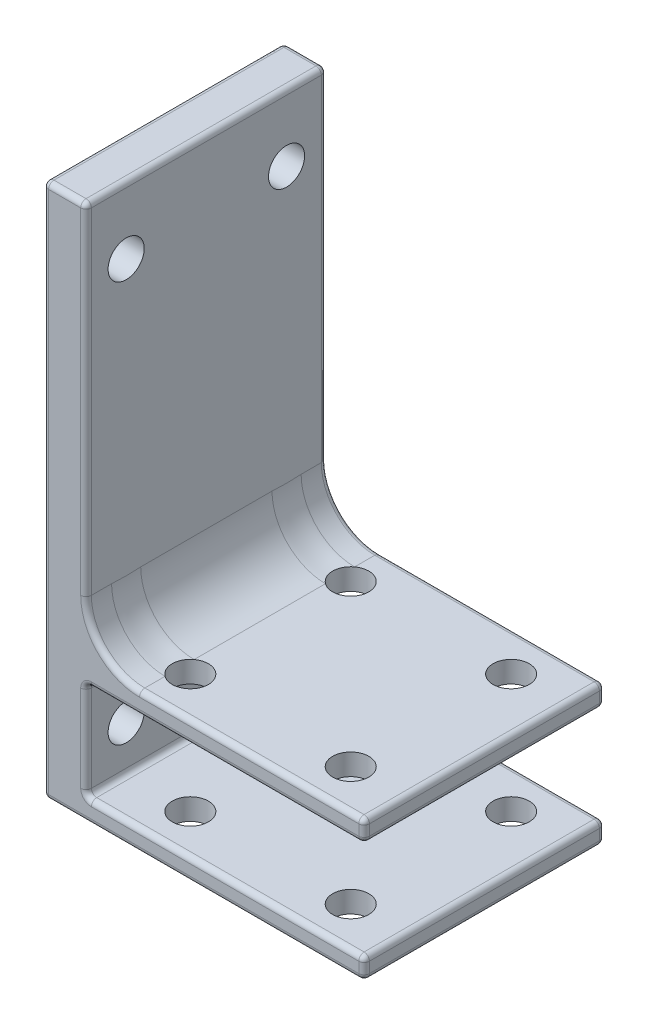
SolidWorks part; units mm, degrees
material "Nylon 6/10"
ref_plane "Front Plane" through (0, 0, 0) normal (0, 0, 1) x (1, 0, 0)
ref_plane "Top Plane" through (0, 0, 0) normal (0, 1, 0) x (1, 0, 0)
ref_plane "Right Plane" through (0, 0, 0) normal (1, 0, 0) x (0, 0, -1)
sketch "Sketch1" plane through (0, 0, 0) normal (0, 0, 1) x (1, 0, 0)
  line L0 (0, 0) -> (0, 100)
  line L1 (0, 100) -> (8, 100)
  line L2 (8, 100) -> (8, 4)
  line L3 (8, 4) -> (60, 4)
  line L4 (60, 4) -> (60, 0)
  line L5 (60, 0) -> (0, 0)
  dimension "D1" = 4
  dimension "D2" = 60
  dimension "D3" = 8
  dimension "D4" = 100
extrude "base" add sketch "Sketch1" along normal blind 45
sketch "Sketch2" plane through (8, 0, 0) normal (1, 0, 0) x (0, 0, -1)
  line L0 (-45, 4) -> (-45, 100) construction
  line L1 (-45, 26.25) -> (0, 26.25)
  line L2 (-45, 26.25) -> (-45, 22.25)
  line L3 (-45, 22.25) -> (0, 22.25)
  line L4 (0, 26.25) -> (0, 22.25)
  line L5 (0, 4) -> (0, 100) construction
  line L6 (-45, 4) -> (0, 4) construction
  dimension "D1" = 4
  dimension "D2" = 18.25
extrude "top skin" add sketch "Sketch2" along normal up to surface (52 mm away) up to face at (60, 2, 22.5)
hole_wizard "slider bolt hole pattern" positions "Sketch3" profile "Sketch4" hole size "1/4" standard "ANSI Inch" end condition through all
sketch "Sketch3" plane through (8, 0, 0) normal (1, 0, 0) x (0, 0, -1)
  line L1 (-37.5, 87.5) -> (-7.5, 87.5)
  line L2 (-37.5, 87.5) -> (-37.5, 12.5)
  line L3 (-37.5, 12.5) -> (-7.5, 12.5)
  line L4 (-7.5, 87.5) -> (-7.5, 12.5)
  line L5 (-22.5, 12.5) -> (-22.5, 0) construction
  line L6 (-45, 0) -> (0, 0) construction
  line L8 (-22.5, 87.5) -> (-22.5, 100) construction
  line L9 (-45, 100) -> (0, 100) construction
  point P0 (-37.5, 87.5)
  point P1 (-7.5, 12.5)
  point P60 (-37.5, 12.5)
  point P61 (-7.5, 87.5)
  dimension "D1" = 75
  dimension "D2" = 30
sketch "Sketch4" plane through (8, 87.5, 37.5) normal (0, 1, 0) x (0, 0, -1)
  line L0 (0, 0) -> (0, 8)
  line L1 (0, 8) -> (3.3782, 8)
  line L2 (3.3782, 8) -> (3.3782, 0)
  line L5 (3.3782, 0) -> (0, 0)
  line L11 (0, -6.35) -> (0, 107.95) construction
  dimension "Thru Hole Dia." = 6.7564
  dimension "Thru Hole Depth" = 8
hole_wizard "desktop bolt hole pattern" positions "Sketch5" profile "Sketch6" hole size "1/4" standard "ANSI Inch" end condition through all
sketch "Sketch5" plane through (0, 26.25, 0) normal (0, 1, 0) x (1, 0, 0)
  line L1 (20, -7.5) -> (50, -7.5)
  line L2 (20, -7.5) -> (20, -37.5)
  line L3 (20, -37.5) -> (50, -37.5)
  line L4 (50, -7.5) -> (50, -37.5)
  line L5 (50, -22.5) -> (60, -22.5)
  line L6 (60, -45) -> (60, 0) construction
  point P1 (20, -7.5)
  point P2 (50, -37.5)
  point P97 (20, -37.5)
  point P98 (50, -7.5)
  dimension "D2" = 30
  dimension "D1" = 10
  dimension "D3" = 30
sketch "Sketch6" plane through (20, 26.25, 7.5) normal (1, 0, 0) x (0, 0, 1)
  line L0 (0, 0) -> (0, 26.25)
  line L1 (0, 26.25) -> (3.3782, 26.25)
  line L2 (3.3782, 26.25) -> (3.3782, 0)
  line L5 (3.3782, 0) -> (0, 0)
  line L11 (0, -6.35) -> (0, 107.95) construction
  dimension "Thru Hole Dia." = 6.7564
  dimension "Thru Hole Depth" = 26.25
fillet "visible corner fillet" radius 10 1 edges at (8, 26.25, 22.5)
fillet "break other corners" radius 1 31 edges at (60, 0, 22.5) (60, 4, 22.5) (60, 26.25, 22.5) (60, 22.25, 22.5) (60, 2, 0) (34, 4, 0) (8, 13.125, 0) (34, 22.25, 0) (60, 24.25, 0) (39, 26.25, 0) (10.9289, 29.1789, 0) (8, 68.125, 0) (4, 100, 0) (30, 0, 0) (0, 100, 22.5) (0, 0, 22.5) (0, 50, 0) (0, 50, 45) (4, 100, 45) (8, 68.125, 45) (10.9289, 29.1789, 45) (39, 26.25, 45) (60, 24.25, 45) (34, 22.25, 45) (8, 13.125, 45) (34, 4, 45) (60, 2, 45) (30, 0, 45) (8, 4, 22.5) (8, 22.25, 22.5) (8, 100, 22.5)
equation "\"board_thickness\" = 18mm"
equation "\"way_width\"= 75mm"
equation "\"way_thickness\"= 50mm"
equation "\"radial_clearance\"= 0.1mm"
equation "\"slider_width\"= \"way_width\"-2* \"radial_clearance\""
equation "\"slider_thickness\" = \"way_thickness\" - 2 * \"radial_clearance\""
equation "\"column_width\"= \"way_width\" + 2 * \"board_thickness\""
equation "\"boxway_slot_width\" = 50mm"
equation "\"keeper_rail_width\" = (\"column_width\" - \"boxway_slot_width\")/2"
equation "\"slider_length\" = 125mm"
equation "\"nut_diameter\"= 22mm"
equation "\"nut_length\"= 15mm"
equation "\"leadscrew_diameter\"= 10mm"
equation "\"leadscrew_radial_clearance\"= 1mm"
equation "\"bearing_bolt_pattern_width\" = 30mm"
equation "\"bearing_bolt_pattern_height\" = 75mm"
equation "\"desktop_bolt_pattern_width\" = 30mm"
equation "\"desktop_bolt_pattern_height\" = 30mm"
equation "\"bearing_bolt_nut_counterbore_diameter\" = 12mm"
equation "\"bearing_bolt_nut_counterbore_depth\"= 10mm"
equation "\"desktop_depth\"= 500mm"
equation "\"desktop_width\"= 650mm"
equation "\"desktop_thickness\"= 18mm"
equation "\"leg_height\"=100mm"
equation "\"leg_width\"=18mm"
equation "\"leg_length\"=500mm"
equation "\"lap_joint_height\" = 50mm"
equation "\"lap_dowel_diameter\"= 8mm"
equation "\"lap_dowel_hole_z_spacing\"=30"
equation "\"skin_thicknes\"= 4"
equation "\"D1@Sketch1\"=\"skin_thicknes\""
equation "\"D1@Sketch2\"=\"skin_thicknes\""
equation "\"D2@Sketch2\"=\"desktop_thickness\" + 0.25"
equation "\"D1@Sketch3\"=\"bearing_bolt_pattern_height\""
equation "\"D2@Sketch3\"=\"bearing_bolt_pattern_width\""
equation "\"D2@Sketch5\"=\"desktop_bolt_pattern_width\""
equation "\"D3@Sketch5\"=\"desktop_bolt_pattern_height\""
